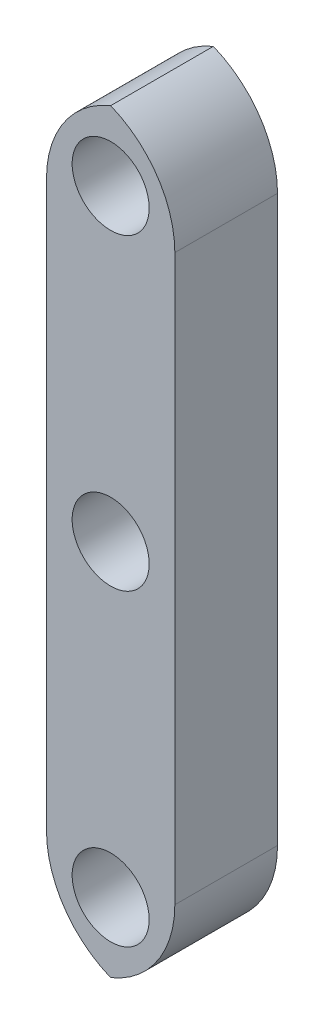
SolidWorks part; units mm, degrees
ref_plane "Front Plane" through (0, 0, 0) normal (1, 0, 0) x (0, 1, 0)
ref_plane "Top Plane" through (0, 0, 0) normal (0, 0, 1) x (0, 1, 0)
ref_plane "Right Plane" through (0, 0, 0) normal (0, 1, 0) x (-1, 0, 0)
sketch "Sketch3" plane through (0, 0, 0) normal (0, 0, 1) x (0, 1, 0)
  line L1 (0, 0) -> (38.1, 0)
  line L2 (0, 0) -> (0, 6.35)
  line L3 (0, 6.35) -> (38.1, 6.35)
  line L4 (38.1, 0) -> (38.1, 6.35)
  dimension "D1" = 38.1
  dimension "D2" = 6.35
extrude "Boss-Extrude1" add sketch "Sketch3" along normal blind 5.08 contours L3 L4 L1 L2
sketch "Sketch4" plane through (0, 0, 5.08) normal (0, 0, 1) x (0, -1, 0)
  line L0 (0, 0) -> (0, -6.35) construction
  line L1 (0, -6.35) -> (-38.1, -6.35) construction
  circle A0 centre (-3.81, -3.175) radius 1.905
  circle A1 centre (-19.05, -3.175) radius 1.905
  circle A2 centre (-34.29, -3.175) radius 1.905
  point P0 (0, -3.175)
  point P1 (-19.05, -6.35)
  point P12 (0, 0)
  point P13 (0, 0)
  dimension "D1" = 3.81
  dimension "D2" = 15.24
  dimension "D3" = 15.24
extrude "Cut-Extrude1" cut sketch "Sketch4" against normal through all
fillet "Fillet2" radius 5.08 4 edges at (0, 38.1, 2.54) (-6.35, 38.1, 2.54) (0, 0, 2.54) (-6.35, 0, 2.54)
